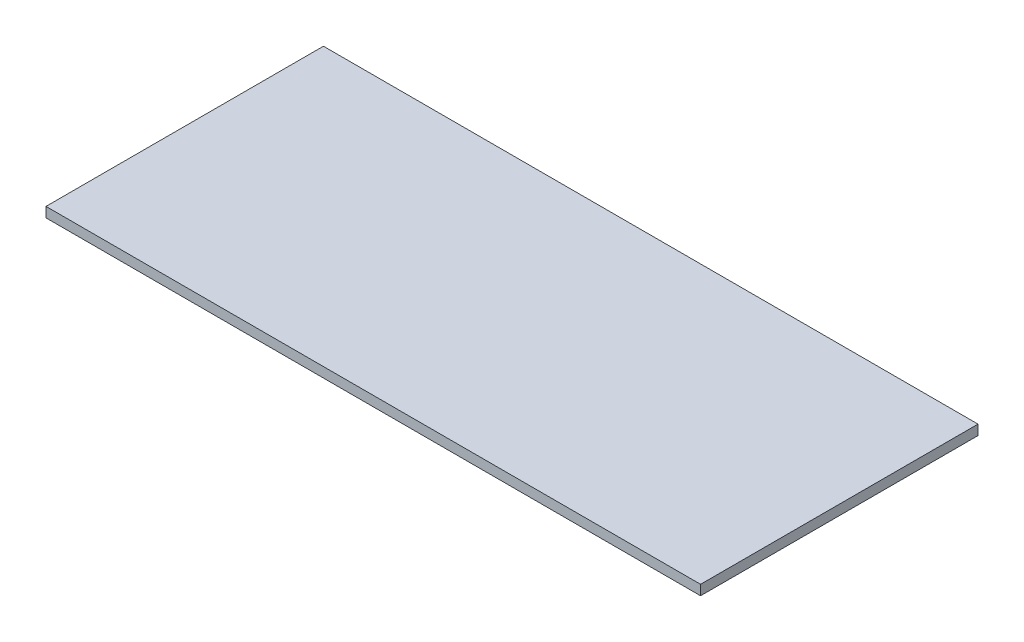
SolidWorks part; units mm, degrees
ref_plane "Front" through (0, 0, 0) normal (0, 0, 1) x (1, 0, 0)
ref_plane "Top" through (0, 0, 0) normal (0, 1, 0) x (1, 0, 0)
ref_plane "Right" through (0, 0, 0) normal (1, 0, 0) x (0, 0, -1)
sketch "Эскиз1" plane through (0, 0, 0) normal (0, 1, 0) x (1, 0, 0)
  line L1 (103, 167) -> (497, 167)
  line L2 (103, 167) -> (103, 0)
  line L3 (103, 0) -> (497, 0)
  line L4 (497, 167) -> (497, 0)
  dimension "D1" = 167
  dimension "D2" = 394
extrude "Бобышка-Вытянуть1" add sketch "Эскиз1" along normal blind 6
